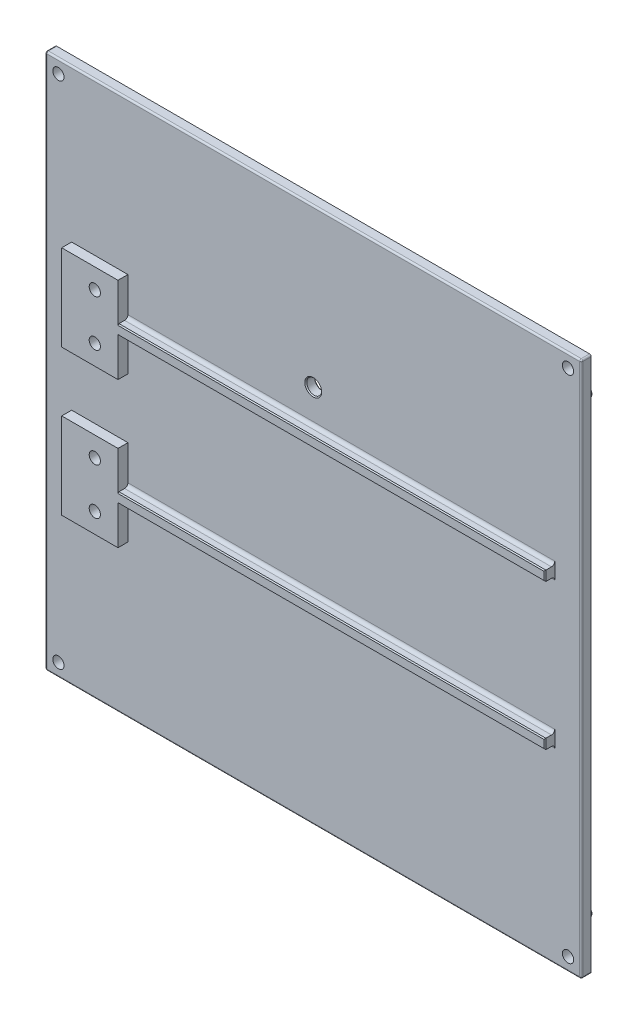
SolidWorks part; units mm, degrees
ref_plane "Спереди" through (0, 0, 0) normal (0, 0, 1) x (1, 0, 0)
ref_plane "Сверху" through (0, 0, 0) normal (0, 1, 0) x (1, 0, 0)
ref_plane "Справа" through (0, 0, 0) normal (1, 0, 0) x (0, 0, -1)
other "Configuration Table"
sketch "Эскиз1" plane through (0, 0, 0) normal (0, 0, 1) x (1, 0, 0)
  line L1 (-81, -81) -> (81, -81)
  line L2 (-81, -81) -> (-81, 81)
  line L3 (-81, 81) -> (81, 81)
  line L4 (81, -81) -> (81, 81)
  line L5 (-81, -81) -> (81, 81) construction
  line L6 (-81, 81) -> (81, -81) construction
  point P0 (0, 0)
  dimension "D1" = 162
  dimension "D2" = 162
extrude "Основа" add sketch "Эскиз1" along normal blind 3
sketch "Эскиз2" plane through (0, 0, 0) normal (0, 0, -1) x (-1, 0, 0)
  line L0 (-81, -81) -> (-81, 81) construction
  line L1 (-81, 81) -> (81, 81) construction
  circle A0 centre (-77, 68) radius 1.5
  dimension "D1" = 3
  dimension "D2" = 4
  dimension "D3" = 13
extrude "Штифт" add sketch "Эскиз2" along normal blind 3
mirror "Зеркальные штифты" about plane through (0, 0, 0) normal (1, 0, 0) of "Штифт" second plane through (0, 0, 0) second plane normal (0, 1, 0)
chamfer "Фаска на штифты" distance 0.3 angle 45 4 edges at (75.5, 68, -3) (75.5, -68, -3) (-78.5, 68, 0) (-75.5, -68, -3)
sketch "Эскиз3" plane through (0, 0, 0) normal (0, 0, -1) x (-1, 0, 0)
  line L0 (-81, 81) -> (81, 81) construction
  line L1 (-81, -81) -> (-81, 81) construction
  circle A0 centre (-77, 77) radius 1.7
  dimension "D1" = 3.4
  dimension "D2" = 4
  dimension "D3" = 4
extrude "Вырез" cut sketch "Эскиз3" against normal through all
mirror "Зеркальные вырезы" about plane through (0, 0, 0) normal (1, 0, 0) of "Вырез" second plane through (0, 0, 0) second plane normal (0, 1, 0)
sketch "Эскиз4" plane through (0, 0, 3) normal (0, 0, 1) x (1, 0, 0)
  line L1 (-73, 35) -> (-53, 35)
  line L2 (-73, 35) -> (-73, 9)
  line L3 (-73, 9) -> (-53, 9)
  line L4 (-53, 35) -> (-53, 9)
  line L5 (-73, 35) -> (-53, 9) construction
  line L6 (-73, 9) -> (-53, 35) construction
  point P0 (-63, 22)
  dimension "D1" = 26
  dimension "D2" = 20
  dimension "D3" = 63
  dimension "D4" = 22
extrude "Площадка" add sketch "Эскиз4" along normal blind 3
sketch "Эскиз5" plane through (0, 0, 6) normal (0, 0, 1) x (1, 0, 0)
  line L0 (-63, 35) -> (-63, 9) construction
  line L1 (-53, 35) -> (-73, 35) construction
  line L2 (-53, 35) -> (-73, 35) construction
  line L3 (-73, 9) -> (-53, 9) construction
  line L4 (-73, 22) -> (-53, 22) construction
  line L5 (-73, 35) -> (-73, 9) construction
  line L7 (-53, 9) -> (-53, 35) construction
  circle A0 centre (-63, 29) radius 1.7
  circle A1 centre (-63, 15) radius 1.7
  point P6 (-63, 35)
  dimension "D1" = 3.4
  dimension "D2" = 6
extrude "Вырезы для уголков" cut sketch "Эскиз5" against normal through all
mirror "Зеркальное отражение3" about plane through (0, 0, 0) normal (0, 1, 0) of "Вырезы для уголков", "Площадка"
sketch "Эскиз6" plane through (0, 0, 3) normal (0, 0, 1) x (1, 0, 0)
  line L0 (0, 81) -> (0, -81) construction
  line L1 (81, 81) -> (-81, 81) construction
  line L3 (-81, -81) -> (81, -81) construction
  circle A0 centre (0, 33.5) radius 2.25
  dimension "D1" = 4.5
  dimension "D2" = 0
  dimension "D3" = 33.5
extrude "Вырезы для проводов" cut sketch "Эскиз6" against normal through all
sketch "Эскиз7" plane through (0, 0, 0) normal (0, 0, -1) x (-1, 0, 0)
  line L1 (66.3486, 29) -> (64.6743, 31.9)
  line L2 (64.6743, 31.9) -> (61.3257, 31.9)
  line L3 (61.3257, 31.9) -> (59.6514, 29)
  line L4 (59.6514, 29) -> (61.3257, 26.1)
  line L5 (61.3257, 26.1) -> (64.6743, 26.1)
  line L6 (64.6743, 26.1) -> (66.3486, 29)
  circle A0 centre (63, 29) radius 2.9 construction
  circle A1 centre (63, 29) radius 1.7 construction
  dimension "D1" = 5.8
extrude "Карман для выреза под площадкой" cut sketch "Эскиз7" against normal blind 2.6
pattern_linear "Карман2" count 2 spacing 14 along (0, -1, 0) of "Карман для выреза под площадкой"
mirror "Зеркальные карманы" about plane through (0, 0, 0) normal (0, 1, 0) of "Карман для выреза под площадкой", "Карман2"
sketch "Эскиз8" plane through (0, 0, 6) normal (0, 0, 1) x (1, 0, 0)
  line L0 (-73, 9) -> (-53, 9) construction
  line L1 (-53, 35) -> (-56, 35)
  line L2 (-53, 35) -> (-53, 9)
  line L3 (-53, 9) -> (-56, 9)
  line L4 (-56, 35) -> (-56, 9)
  dimension "D1" = 3
extrude "Подрезка площадки" cut sketch "Эскиз8" against normal blind 3
mirror "Зеркальная подрезка" about plane through (0, 0, 0) normal (0, 1, 0) of "Подрезка площадки"
sketch "Эскиз10" plane through (0, 0, 3) normal (0, 0, 1) x (1, 0, 0)
  line L0 (81, -81) -> (81, 81) construction
  line L1 (-56, 23.5) -> (73, 23.5)
  line L2 (-56, 23.5) -> (-56, 20.5)
  line L3 (-56, 20.5) -> (73, 20.5)
  line L4 (73, 23.5) -> (73, 20.5)
  line L5 (-56, 23.5) -> (73, 20.5) construction
  line L6 (-56, 20.5) -> (73, 23.5) construction
  line L7 (-56, 35) -> (-56, 9) construction
  line L8 (-73, 35) -> (-56, 9) construction
  line L9 (-73, 9) -> (-56, 35) construction
  point P0 (8.5, 22)
  point P13 (-64.5, 22)
  dimension "D1" = 8
  dimension "D2" = 3
extrude "Поддержка" add sketch "Эскиз10" along normal blind 3
mirror "Зеркальная поддержка" about plane through (0, 0, 0) normal (0, 1, 0) of "Поддержка"
fillet "Скругление2" radius 1 4 edges at (8.5, -20.5, 3) (8.5, -23.5, 3) (8.5, 20.5, 3) (8.5, 23.5, 3)
chamfer "Фаска2" distance 0.3 angle 45 4 edges at (8.5, -20.5, 6) (8.5, -23.5, 6) (8.5, 23.5, 6) (8.5, 20.5, 6)
chamfer "Фаска3" distance 0.3 angle 45 2 edges at (73, 22, 6) (73, -22, 6)
chamfer "Фаска4" distance 0.3 angle 45 2 edges at (-2.25, 33.5, 0) (2.25, 33.5, 3)
fillet "Скругление3" radius 0.5 4 edges at (0, -81, 3) (81, 0, 3) (0, 81, 3) (-81, 0, 3)
fillet "Скругление5" radius 0.5 8 edges at (80.8536, -80.8536, 2.8536) (80.8536, 80.8536, 2.8536) (-80.8536, 80.8536, 2.8536) (81, -81, 1.25) (81, 81, 1.25) (-81, 81, 1.25) (-80.8536, -80.8536, 2.8536) (-81, -81, 1.25)
